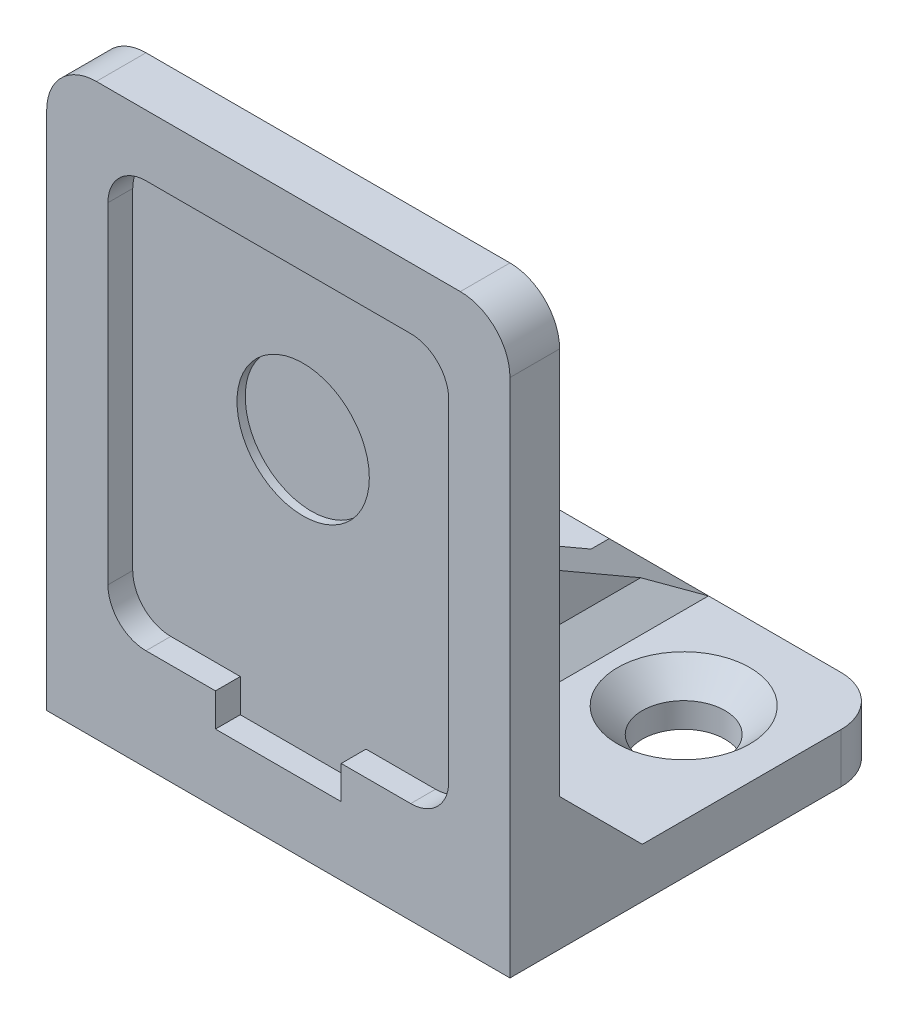
SolidWorks part; units mm, degrees
ref_plane "Plano frontal" through (0, 0, 0) normal (0, 0, 1) x (1, 0, 0)
ref_plane "Plano superior" through (0, 0, 0) normal (0, 1, 0) x (1, 0, 0)
ref_plane "Plano direito" through (0, 0, 0) normal (1, 0, 0) x (0, 0, -1)
sketch "Esboço1" plane through (0, 0, 0) normal (0, 0, 1) x (1, 0, 0)
  line L0 (3.8504, -9.4118) -> (8.0504, -9.4118)
  line L1 (10.0504, -7.4118) -> (10.0504, 12.5882)
  line L2 (8.0504, 14.5882) -> (-7.9496, 14.5882)
  line L3 (-9.9496, 12.5882) -> (-9.9496, -7.4118)
  line L4 (-7.9496, -9.4118) -> (-3.7496, -9.4118)
  line L5 (-3.4496, -9.7118) -> (-3.4496, -11.4118)
  line L6 (-3.4496, -11.4118) -> (3.5504, -11.4118)
  line L7 (3.5504, -11.4118) -> (3.5504, -9.7118)
  line L8 (-18.3173, -15.8418) -> (48.171, -15.8418)
  arc A0 (8.0504, -9.4118) -> (10.0504, -7.4118) centre (8.0504, -7.4118) ccw
  arc A1 (10.0504, 12.5882) -> (8.0504, 14.5882) centre (8.0504, 12.5882) ccw
  arc A2 (-7.9496, 14.5882) -> (-9.9496, 12.5882) centre (-7.9496, 12.5882) ccw
  arc A3 (-9.9496, -7.4118) -> (-7.9496, -9.4118) centre (-7.9496, -7.4118) ccw
  arc A4 (-3.4496, -9.7118) -> (-3.7496, -9.4118) centre (-3.7496, -9.7118) ccw
  arc A5 (3.8504, -9.4118) -> (3.5504, -9.7118) centre (3.8504, -9.7118) ccw
  dimension "D1" = 6.43
  dimension "D2" = 20
sketch "Esboço2" plane through (0, 0, 0) normal (0, 0, 1) x (1, 0, 0)
  line L0 (-18.3173, -15.8418) -> (48.171, -15.8418) construction
  line L1 (-13.9496, 18.5882) -> (14.0504, 18.5882)
  line L2 (-13.9496, 18.5882) -> (-13.9496, -15.8418)
  line L3 (-13.9496, -15.8418) -> (14.0504, -15.8418)
  line L4 (14.0504, 18.5882) -> (14.0504, -15.8418)
  line L5 (8.0504, 14.8882) -> (-7.9496, 14.8882)
  line L6 (-10.2496, 12.5882) -> (-10.2496, -7.4118)
  line L7 (-7.9496, -9.7118) -> (-3.7496, -9.7118)
  line L17 (-3.7496, -9.7118) -> (-3.7496, -11.7118)
  line L19 (-3.7496, -11.7118) -> (3.8504, -11.7118)
  line L20 (3.8504, -11.7118) -> (3.8504, -9.7118)
  line L21 (3.8504, -9.7118) -> (8.0504, -9.7118)
  line L22 (10.3504, -7.4118) -> (10.3504, 12.5882)
  arc A0 (-7.9496, 14.8882) -> (-10.2496, 12.5882) centre (-7.9496, 12.5882) ccw
  arc A1 (-10.2496, -7.4118) -> (-7.9496, -9.7118) centre (-7.9496, -7.4118) ccw
  arc A4 (8.0504, -9.7118) -> (10.3504, -7.4118) centre (8.0504, -7.4118) ccw
  arc A5 (10.3504, 12.5882) -> (8.0504, 14.8882) centre (8.0504, 12.5882) ccw
extrude "Ressalto-extrusão1" add sketch "Esboço2" along normal blind 3
fillet "Filete1" radius 3 2 edges at (-13.9496, 18.5882, 1.5) (14.0504, 18.5882, 1.5)
sketch "Esboço3" plane through (0, 0, 0) normal (0, 0, -1) x (-1, 0, 0)
  line L0 (13.9496, 15.5882) -> (13.9496, -15.8418) construction
  line L1 (18.3173, -15.8418) -> (-48.171, -15.8418) construction
  line L2 (-14.0504, -15.8418) -> (-14.0504, 15.5882) construction
  line L3 (-11.0504, 18.5882) -> (10.9496, 18.5882) construction
  line L4 (13.9496, 15.5882) -> (13.9496, -15.8418)
  line L5 (13.9496, -15.8418) -> (-14.0504, -15.8418)
  line L6 (-14.0504, -15.8418) -> (-14.0504, 15.5882)
  line L7 (-11.0504, 18.5882) -> (10.9496, 18.5882)
  arc A0 (13.9496, 15.5882) -> (10.9496, 18.5882) centre (10.9496, 15.5882) ccw construction
  arc A1 (-11.0504, 18.5882) -> (-14.0504, 15.5882) centre (-11.0504, 15.5882) ccw construction
  arc A2 (13.9496, 15.5882) -> (10.9496, 18.5882) centre (10.9496, 15.5882) ccw
  arc A3 (-11.0504, 18.5882) -> (-14.0504, 15.5882) centre (-11.0504, 15.5882) ccw
extrude "Ressalto-extrusão2" add sketch "Esboço3" against normal blind 1.5
sketch "Esboço4" plane through (0, 0, 1.5) normal (0, 0, 1) x (1, 0, 0)
  line L0 (-10.2496, 2.5882) -> (10.0504, 2.5882) construction
  line L1 (-10.2496, 12.5882) -> (-10.2496, -7.4118) construction
  line L2 (10.0504, -7.4118) -> (10.0504, 12.5882) construction
  line L3 (0.0504, 14.8882) -> (0.0504, -11.7118) construction
  line L4 (8.0504, 14.8882) -> (-7.9496, 14.8882) construction
  line L5 (-3.7496, -11.7118) -> (3.8504, -11.7118) construction
sketch "Esboço5" plane through (0, 0, 0) normal (0, 0, -1) x (-1, 0, 0)
  line L0 (13.9496, 15.5882) -> (13.9496, -15.8418) construction
  line L1 (-14.0504, -15.8418) -> (13.9496, -15.8418)
  line L2 (-14.0504, -15.8418) -> (-14.0504, -12.8418)
  line L3 (-14.0504, -12.8418) -> (13.9496, -12.8418)
  line L4 (13.9496, -15.8418) -> (13.9496, -12.8418)
  dimension "D1" = 3
extrude "Ressalto-extrusão3" add sketch "Esboço5" along normal blind 20
sketch "Esboço6" plane through (0, -12.8418, 0) normal (0, 1, 0) x (1, 0, 0)
  line L0 (-13.9496, 13.5) -> (-7.9496, 13.5) construction
  line L3 (-13.9496, 0) -> (14.0504, 0) construction
  line L4 (-13.9496, 20) -> (14.0504, 20) construction
  line L5 (0.0504, 20) -> (0.0504, 3.7408) construction
  line L9 (8.0504, 13.5) -> (14.0504, 13.5) construction
  circle A0 centre (-7.9496, 13.5) radius 2.5
  circle A1 centre (8.0504, 13.5) radius 2.5
  dimension "D1" = 5
  dimension "D2" = 5
  dimension "D3" = 13.5
  dimension "D4" = 6
  dimension "D5" = 6
extrude "Corte-extrusão1" cut sketch "Esboço6" against normal blind 10
fillet "Filete2" radius 3 2 edges at (-13.9496, -14.3418, -20) (14.0504, -14.3418, -20)
ref_plane "Plano2" through (0.0504, 0, 0) normal (1, 0, 0) x (0, 0, -1)
sketch "Esboço7" plane through (0.0504, 0, 0) normal (1, 0, 0) x (0, 0, -1)
  line L1 (0, -1.2948) -> (0, -12.8418)
  line L2 (0, -12.8418) -> (20, -12.8418)
  line L4 (0, -12.8418) -> (0, 15.5882) construction
  line L5 (20, -12.8418) -> (0, -1.2948)
  dimension "D1" = 30
extrude "Ressalto-extrusão4" add sketch "Esboço7" along normal mid plane 3
chamfer "Chanfro1" distance 1.5 angle 45 4 edges at (1.5504, -12.8418, -10) (-1.4496, -12.8418, -10) (1.5504, -7.0683, 0) (-1.4496, -7.0683, 0)
chamfer "Chanfro2" distance 1.5 angle 45 2 edges at (5.5504, -12.8418, -13.5) (-10.4496, -12.8418, -13.5)
sketch "Esboço8" plane through (0, 0, 1.5) normal (0, 0, 1) x (1, 0, 0)
  circle A0 centre (0.0504, 4.5882) radius 4
extrude "Corte-extrusão2" cut sketch "Esboço8" against normal blind 0.5
chamfer "Chanfro3" distance 5 angle 45 2 edges at (-8.4496, -12.8418, 0) (8.5504, -12.8418, 0)
sketch "Esboço9" plane through (0, 0, 0) normal (0, 0, -1) x (-1, 0, 0)
  line L4 (-11.0504, 18.5882) -> (10.9496, 18.5882) construction
  line L6 (-6.5504, -12.8418) -> (-6.5504, 18.5882)
  line L8 (-9.5504, -12.8418) -> (-9.5504, 18.5882)
  line L12 (9.4496, -12.8418) -> (9.4496, 18.5882)
  line L14 (6.4496, -12.8418) -> (6.4496, 18.5882)
  line L17 (-9.5504, 18.5882) -> (-6.5504, 18.5882)
  line L18 (10.9496, -12.8418) -> (2.9496, -12.8418) construction
  line L19 (-3.0504, -12.8418) -> (-14.0504, -12.8418) construction
  line L20 (9.4496, -12.8418) -> (6.4496, -12.8418)
  line L21 (-6.5504, -12.8418) -> (-9.5504, -12.8418)
  line L22 (6.4496, 18.5882) -> (9.4496, 18.5882)
  point P8 (-8.0504, -5.2999)
  point P13 (7.9496, -1.0978)
extrude "Ressalto-extrusão5" add sketch "Esboço9" along normal blind 0.5
chamfer "Chanfro4" distance 0.5 angle 45 2 edges at (-7.9496, 18.5882, -0.5) (8.0504, 18.5882, -0.5)
